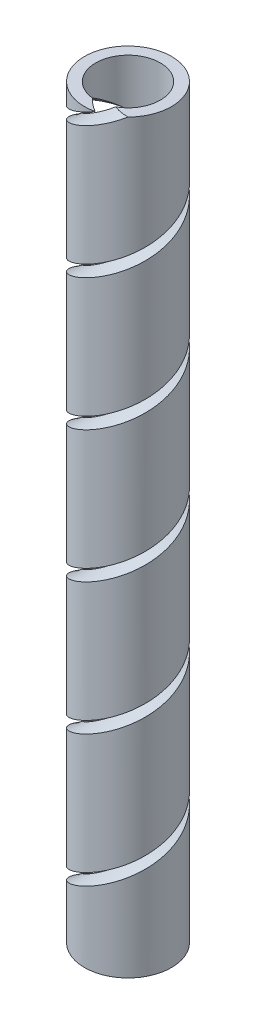
SolidWorks part; units mm, degrees
material "Rubber"
ref_plane "Front" through (0, 0, 0) normal (0, 0, 1) x (1, 0, 0)
ref_plane "Top" through (0, 0, 0) normal (0, 1, 0) x (1, 0, 0)
ref_plane "Right" through (0, 0, 0) normal (1, 0, 0) x (0, 0, -1)
sketch "Sketch1" plane through (0, 0, 0) normal (0, 1, 0) x (1, 0, 0)
  circle A0 centre (0, 0) radius 4.445
  circle A1 centre (0, 0) radius 3.302
  dimension "D1" = 8.89
  dimension "D2" = 6.604
extrude "Boss-Extrude1" add sketch "Sketch1" along normal blind 76.2
sketch "Sketch2" plane through (0, 76.2, 0) normal (0, 1, 0) x (1, 0, 0)
  circle A1 centre (0, 0) radius 4.445
  circle A2 centre (0, 0) radius 4.445
  dimension "D1" = 0
curve "Helix/Spiral1" pitch 13.461 height 77.4008 turns 5.75
sketch "Sketch3" plane through (0, 76.2, 0) normal (0, 1, 0) x (1, 0, 0)
  circle A0 centre (0, 0) radius 4.445 construction
  point P0 (3.1431, -3.1431)
ref_plane "Plane1" through (3.1431, 76.2, 3.1431) normal (-0.637, -0.4342, 0.637) x (0.7709, -0.3588, 0.5263)
sketch "Sketch4" plane through (3.1431, 76.2, 3.1431) normal (-0.637, -0.4342, 0.637) x (0.7709, -0.3588, 0.5263)
  line L1 (0, 0) -> (-2.3288, 0)
  line L2 (0, 0) -> (0, 0.9849)
  line L3 (0, 0.9849) -> (-2.3288, 0.9849)
  line L4 (-2.3288, 0) -> (-2.3288, 0.9849)
  dimension "D1" = 0.9849
  dimension "D2" = 2.3288
sweep "Cut-Sweep1" cut profiles "Sketch4" path "Helix/Spiral1"
